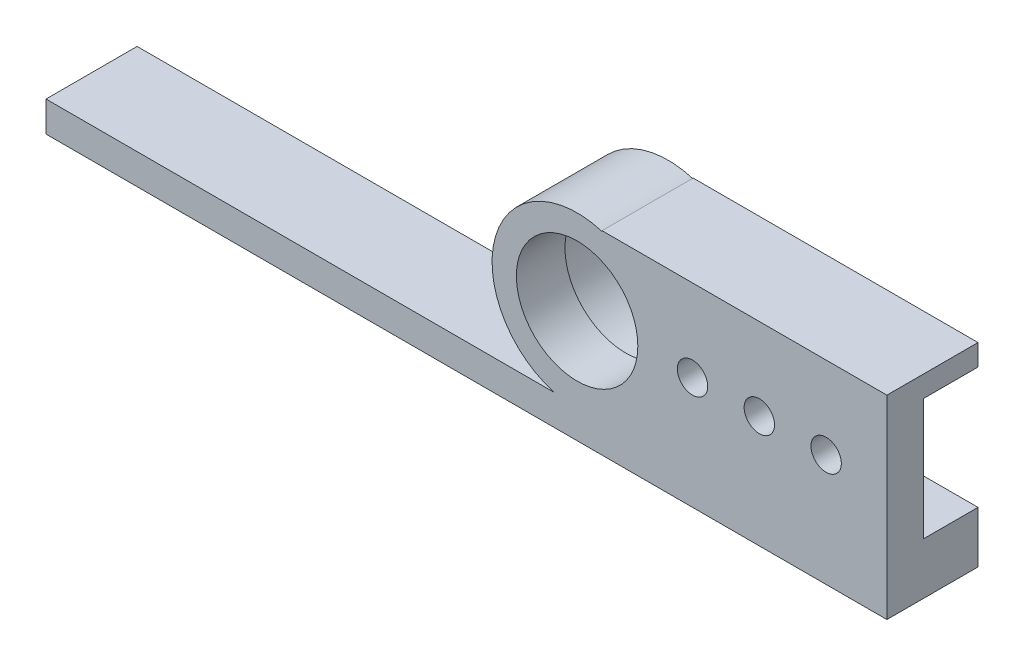
SolidWorks part; units mm, degrees
ref_plane "前视基准面" through (0, 0, 0) normal (0, 0, 1) x (1, 0, 0)
ref_plane "上视基准面" through (0, 0, 0) normal (0, 1, 0) x (1, 0, 0)
ref_plane "右视基准面" through (0, 0, 0) normal (1, 0, 0) x (0, 0, -1)
sketch "草图1" plane through (0, 0, 0) normal (0, 0, 1) x (1, 0, 0)
  line L1 (20, -10) -> (-20, -10)
  line L2 (20, -10) -> (20, 10)
  line L3 (20, 10) -> (-20, 10)
  line L4 (-20, -10) -> (-20, 10)
  line L5 (20, -10) -> (-20, 10) construction
  line L6 (20, 10) -> (-20, -10) construction
  point P0 (0, 0)
  dimension "D1" = 40
  dimension "D2" = 20
extrude "凸台-拉伸1" add sketch "草图1" along normal blind 6
sketch "草图2" plane through (0, 0, 6) normal (0, 0, 1) x (1, 0, 0)
  line L0 (20, -10) -> (20, 10) construction
  circle A0 centre (10, 0) radius 2.5
  circle A1 centre (-1, 0) radius 2.5
  circle A2 centre (-12, 0) radius 2.5
  dimension "D1" = 10
  dimension "D2" = 5
  dimension "D3" = 3
extrude "切除-拉伸1" cut sketch "草图2" against normal through all
sketch "草图3" plane through (0, 0, 6) normal (0, 0, 1) x (1, 0, 0)
  line L0 (20, 13.5) -> (20, 10)
  line L1 (20, -13.5) -> (-26.894, -13.5)
  line L3 (20, 13.5) -> (-26.894, 13.5)
  line L4 (-20, 10) -> (-20, -10)
  line L5 (-20, -10) -> (20, -10)
  line L6 (20, -10) -> (20, 10)
  line L7 (20, 10) -> (-20, 10)
  line L8 (-20, 10) -> (-20, -10)
  line L9 (-20, -10) -> (20, -10)
  line L10 (20, -10) -> (20, 10)
  line L11 (20, 10) -> (-20, 10)
  line L12 (-26.894, -13.5) -> (-26.894, 13.5)
  line L13 (20, -10.0394) -> (-26.894, 13.5) construction
  line L14 (20, 10.0394) -> (-26.894, -13.5) construction
  line L15 (20, -10) -> (20, -13.5)
  circle A0 centre (-31, 0) radius 11
  circle A1 centre (-31, 0) radius 14
  point P2 (0, 0)
  line M10 (-20, 10) -> (-20, -10)
  line M11 (-20, -10) -> (20, -10)
  line M13 (20, 10) -> (-20, 10)
  dimension "D3" = 22
  dimension "D4" = 28
  dimension "D2" = 3.5
  dimension "D1" = 0
extrude "凸台-拉伸2" add sketch "草图3" against normal blind 15 contours L3 A1 L1 L12 A0 | A1 L1 L15 M11 M10 | L1 A1 L8 A0 L12 | L8 A1 L3 L12 A0 | L8 A1 | A1 L0 L3 M10 M13 region at (-1.9449, 11.7771, 6) region at (-1.9449, -11.7771, 6) region at (-23.0173, 9.0328, 6) region at (-27.2274, 11.7946, 6) region at (-18.7882, 0, 6) region at (-23.0173, -9.0328, 6)
sketch "草图5" plane through (0, 0, 6) normal (0, 0, 1) x (1, 0, 0)
  circle A0 centre (-31, 0) radius 10
  circle A1 centre (-31, 0) radius 11 construction
  circle A2 centre (-31, 0) radius 11
  dimension "D1" = 20
extrude "凸台-拉伸3" add sketch "草图5" against normal blind 8
sketch "草图6" plane through (0, 0, 6) normal (0, 0, 1) x (1, 0, 0)
  circle A0 centre (-31, 0) radius 8.5
  circle A1 centre (-31, 0) radius 10 construction
  circle A2 centre (-31, 0) radius 10
  dimension "D1" = 17
sketch "草图9" plane through (0, -13.5, 0) normal (0, -1, 0) x (1, 0, 0)
  circle A0 centre (-18.2368, -1.344) radius 5.5352
sketch "草图10" plane through (20, 0, 0) normal (1, 0, 0) x (0, 0, -1)
  line L1 (9, -13.5) -> (-6, -13.5)
  line L2 (9, -13.5) -> (9, -18.5)
  line L3 (9, -18.5) -> (-6, -18.5)
  line L4 (-6, -13.5) -> (-6, -18.5)
  dimension "D1" = 5
extrude "凸台-拉伸4" add sketch "草图10" against normal blind 200
sketch "草图11" plane through (0, 0, 6) normal (0, 0, 1) x (1, 0, 0)
  line L1 (-28.6193, -11.8661) -> (-25.5243, -11.8661)
  line L2 (-28.6193, -11.8661) -> (-28.6193, -14.961)
  line L3 (-28.6193, -14.961) -> (-25.5243, -14.961)
  line L4 (-25.5243, -11.8661) -> (-25.5243, -14.961)
extrude "凸台-拉伸5" add sketch "草图11" against normal through all
sketch "草图13" plane through (0, -18.5, 0) normal (0, -1, 0) x (1, 0, 0)
  line L0 (-164.0842, 6) -> (-164.0842, -9)
  line L1 (-180, 6) -> (20, 6) construction
  line L2 (-164.0842, 123.2983) -> (-164.0842, -246.7017) construction
  line L3 (-180, -9) -> (20, -9) construction
sketch "草图14" plane through (0, -18.5, 0) normal (0, -1, 0) x (1, 0, 0)
  line L0 (-118.4338, -15.7251) -> (-118.4338, 9.3691)
  line L1 (-118.4338, 121.5018) -> (-118.4338, -248.4982) construction
sketch "草图15" plane through (0, -18.5, 0) normal (0, -1, 0) x (1, 0, 0)
  line L1 (-118.4338, -15.7251) -> (-184.1416, -15.7251)
  line L2 (-118.4338, -15.7251) -> (-118.4338, 11.9644)
  line L3 (-118.4338, 11.9644) -> (-184.1416, 11.9644)
  line L4 (-184.1416, -15.7251) -> (-184.1416, 11.9644)
sketch "草图16" plane through (0, -18.5, 0) normal (0, -1, 0) x (1, 0, 0)
  line L0 (-118.4338, -17.1171) -> (-118.4338, 37.1771)
  line L1 (-118.4338, 121.5018) -> (-118.4338, -248.4982) construction
sketch "草图17" plane through (0, -18.5, 0) normal (0, -1, 0) x (1, 0, 0)
  line L1 (-118.4338, -17.1171) -> (-191.9094, -17.1171)
  line L2 (-118.4338, -17.1171) -> (-118.4338, 25.2398)
  line L3 (-118.4338, 25.2398) -> (-191.9094, 25.2398)
  line L4 (-191.9094, -17.1171) -> (-191.9094, 25.2398)
extrude "切除-拉伸2" cut sketch "草图17" against normal through all
